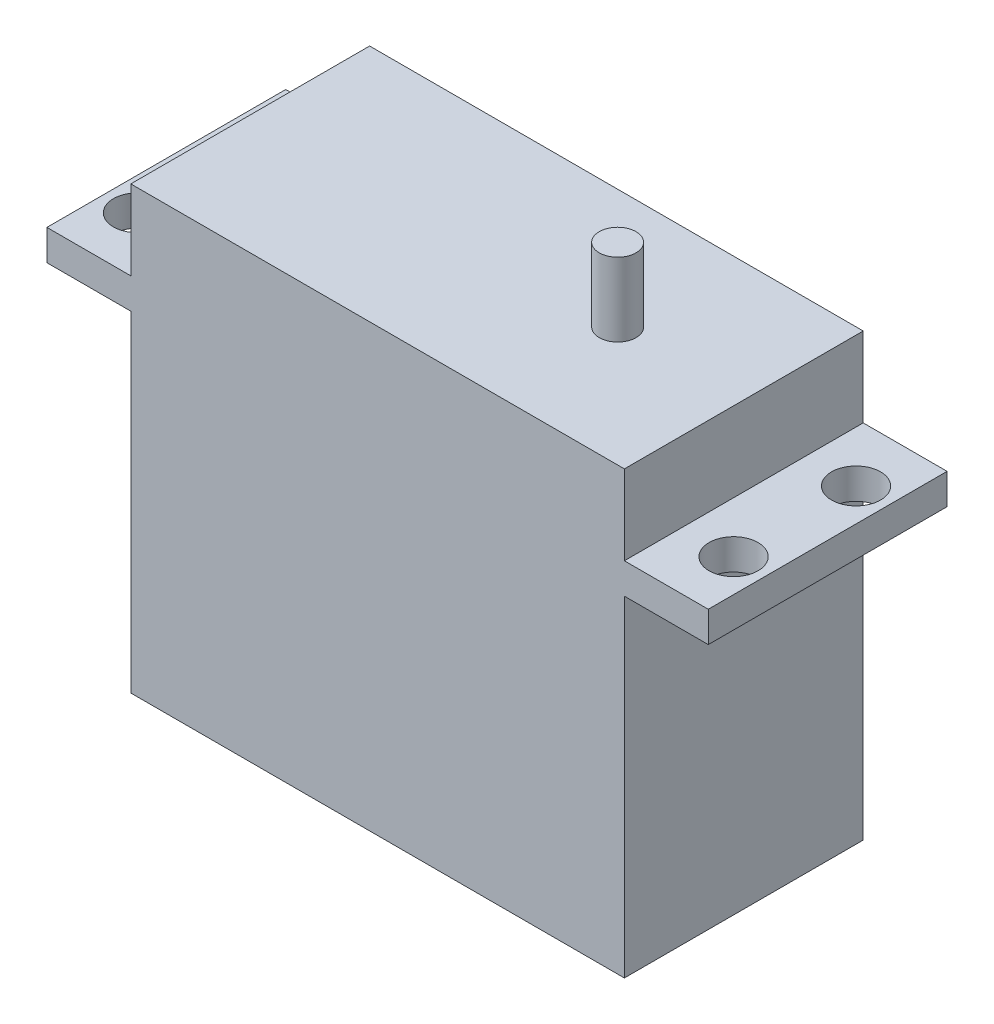
SolidWorks part; units mm, degrees
ref_plane "Front Plane" through (0, 0, 0) normal (0, 0, 1) x (1, 0, 0)
ref_plane "Top Plane" through (0, 0, 0) normal (0, 1, 0) x (1, 0, 0)
ref_plane "Right Plane" through (0, 0, 0) normal (1, 0, 0) x (0, 0, -1)
sketch "Sketch1" plane through (0, 0, 0) normal (0, 1, 0) x (1, 0, 0)
  line L1 (-20.15, 9.75) -> (20.15, 9.75)
  line L2 (-20.15, 9.75) -> (-20.15, -9.75)
  line L3 (-20.15, -9.75) -> (20.15, -9.75)
  line L4 (20.15, 9.75) -> (20.15, -9.75)
  line L5 (-20.15, 9.75) -> (20.15, -9.75) construction
  line L6 (-20.15, -9.75) -> (20.15, 9.75) construction
  point P0 (0, 0)
  dimension "D1" = 40.3
  dimension "D2" = 19.5
extrude "Boss-Extrude1" add sketch "Sketch1" along normal blind 27
sketch "Sketch2" plane through (0, 27, 0) normal (0, 1, 0) x (1, 0, 0)
  line L1 (-27, 9.75) -> (27, 9.75)
  line L2 (-27, 9.75) -> (-27, -9.75)
  line L3 (-27, -9.75) -> (27, -9.75)
  line L4 (27, 9.75) -> (27, -9.75)
  line L5 (-27, 9.75) -> (27, -9.75) construction
  line L6 (-27, -9.75) -> (27, 9.75) construction
  point P0 (0, 0)
  dimension "D1" = 19.5
  dimension "D2" = 54
extrude "Boss-Extrude2" add sketch "Sketch2" along normal blind 2.5
sketch "Sketch3" plane through (0, 29.5, 0) normal (0, 1, 0) x (1, 0, 0)
  line L1 (-20.15, 9.75) -> (20.15, 9.75)
  line L2 (-20.15, 9.75) -> (-20.15, -9.75)
  line L3 (-20.15, -9.75) -> (20.15, -9.75)
  line L4 (20.15, 9.75) -> (20.15, -9.75)
  line L5 (-20.15, 9.75) -> (20.15, -9.75) construction
  line L6 (-20.15, -9.75) -> (20.15, 9.75) construction
  point P0 (0, 0)
  dimension "D1" = 19.5
  dimension "D2" = 40.3
extrude "Boss-Extrude3" add sketch "Sketch3" along normal blind 6.5
sketch "Sketch4" plane through (0, 36, 0) normal (0, 1, 0) x (1, 0, 0)
  line L0 (-20.15, 0) -> (20.15, 0) construction
  line L1 (-20.15, 9.75) -> (-20.15, -9.75) construction
  line L2 (20.15, -9.75) -> (20.15, 9.75) construction
  line L3 (0, 9.75) -> (0, -9.75) construction
  line L4 (20.15, 9.75) -> (-20.15, 9.75) construction
  line L5 (-20.15, -9.75) -> (20.15, -9.75) construction
  circle A0 centre (9.85, 0) radius 1.5
  dimension "D2" = 3
  dimension "D1" = 9.85
extrude "Boss-Extrude4" add sketch "Sketch4" along normal blind 6
sketch "Sketch5" plane through (0, 29.5, 0) normal (0, 1, 0) x (1, 0, 0)
  line L0 (-27, 0) -> (27, 0) construction
  line L1 (-27, 9.75) -> (-27, -9.75) construction
  line L2 (27, -9.75) -> (27, 9.75) construction
  line L3 (0, 0) -> (0, 15.0528) construction
  line L4 (-24.315, 0) -> (-24.315, 14.5347) construction
  circle A0 centre (-24.315, 5) radius 2
  circle A1 centre (-24.315, -5) radius 2
  circle A2 centre (24.315, -5) radius 2
  circle A3 centre (24.315, 5) radius 2
  dimension "D2" = 4
  dimension "D1" = 24.315
  dimension "D3" = 5
extrude "Cut-Extrude1" cut sketch "Sketch5" against normal through all both and the other way through all
